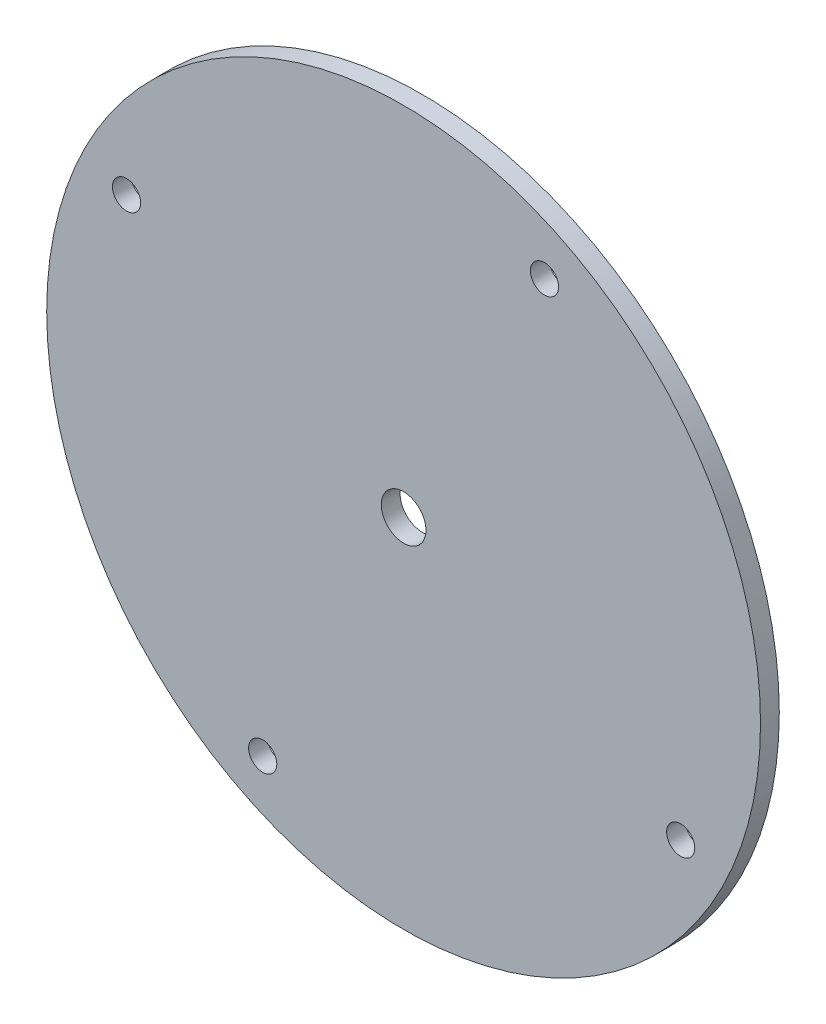
SolidWorks part; units mm, degrees
material "1060 Alloy"
ref_plane "Front Plane" through (0, 0, 0) normal (0, 0, 1) x (1, 0, 0)
ref_plane "Top Plane" through (0, 0, 0) normal (0, 1, 0) x (1, 0, 0)
ref_plane "Right Plane" through (0, 0, 0) normal (1, 0, 0) x (0, 0, -1)
sketch "Sketch1" plane through (0, 0, 0) normal (0, 0, 1) x (1, 0, 0)
  line L5 (50, -50) -> (-50, 50) construction
  line L6 (50, 50) -> (-50, -50) construction
  line L31 (24.5, 59) -> (27.25, 54.2369)
  line L32 (27.25, 54.2369) -> (32.75, 54.2369)
  line L33 (32.75, 54.2369) -> (35.5, 59)
  line L36 (-38.9, 50) -> (38.9, 50) construction
  line L50 (0, -76) -> (0, 122.6166) construction
  line L51 (-76, 0) -> (103.3867, 0) construction
  line L52 (35.5, 59) -> (32.75, 63.7631)
  line L53 (32.75, 63.7631) -> (27.25, 63.7631)
  line L54 (27.25, 63.7631) -> (24.5, 59)
  line L55 (-59, 24.5) -> (-54.2369, 27.25)
  line L56 (-54.2369, 27.25) -> (-54.2369, 32.75)
  line L57 (-54.2369, 32.75) -> (-59, 35.5)
  line L58 (-59, 35.5) -> (-63.7631, 32.75)
  line L59 (-63.7631, 32.75) -> (-63.7631, 27.25)
  line L60 (-63.7631, 27.25) -> (-59, 24.5)
  line L61 (59, -24.5) -> (54.2369, -27.25)
  line L62 (54.2369, -27.25) -> (54.2369, -32.75)
  line L96 (54.2369, -32.75) -> (59, -35.5)
  line L97 (59, -35.5) -> (63.7631, -32.75)
  line L98 (63.7631, -32.75) -> (63.7631, -27.25)
  line L99 (63.7631, -27.25) -> (59, -24.5)
  line L100 (-24.5, -59) -> (-27.25, -54.2369)
  line L101 (-27.25, -54.2369) -> (-32.75, -54.2369)
  line L102 (-32.75, -54.2369) -> (-35.5, -59)
  line L103 (-35.5, -59) -> (-32.75, -63.7631)
  line L104 (-32.75, -63.7631) -> (-27.25, -63.7631)
  line L105 (-27.25, -63.7631) -> (-24.5, -59)
  arc A0 (0, 76) -> (-72.0169, -24.281) centre (0, 0) ccw
  circle A1 centre (30, 59) radius 3
  arc A2 (76, 0) -> (0, 76) centre (0, 0) ccw
  arc A3 (-72.0169, -24.281) -> (0, -76) centre (0, 0) ccw
  arc A4 (0, -76) -> (76, 0) centre (0, 0) ccw
  circle A5 centre (59, -30) radius 3
  circle A6 centre (-30, -59) radius 3
  circle A7 centre (-59, 30) radius 3
  circle A8 centre (30, 59) radius 5.5 construction
  circle A9 centre (-59, 30) radius 5.5 construction
  circle A10 centre (59, -30) radius 5.5 construction
  circle A11 centre (-30, -59) radius 5.5 construction
  dimension "D1" = 152
  dimension "D9" = 30
  dimension "D2" = 59
  dimension "D15" = 11
  dimension "D16" = 11
  dimension "D17" = 11
  dimension "D3" = 30
  dimension "D4" = 59
  dimension "D5" = 59
  dimension "D6" = 59
  dimension "D10" = 30
  dimension "D11" = 30
extrude "Boss-Extrude3" add sketch "Sketch1" along normal blind 4 contours A4 A2 A0 A3 L105 L104 L103 L102 L101 L100 L99 L98 L97 L96 L62 L61 L60 L59 L58 L57 L56 L55 L54 L53 L52 L33 L32 L31 | L59 L60 L55 L56 L57 L58 A7 | L53 L54 L31 L32 L33 L52 A1 | L98 L99 L61 L62 L96 L97 A5 | L104 L105 L100 L101 L102 L103 A6 region at (26.001, 61.3088, 0) region at (-61.3088, 26.001, 0) region at (61.3088, -26.001, 0) region at (-26.001, -61.3088, 0) region at (0, 0, 0)
sketch "Sketch2" plane through (0, 0, 4) normal (0, 0, 1) x (1, 0, 0)
  circle A0 centre (0, 0) radius 4.75
  dimension "D1" = 9.5
extrude "Cut-Extrude1" cut sketch "Sketch2" against normal through all
